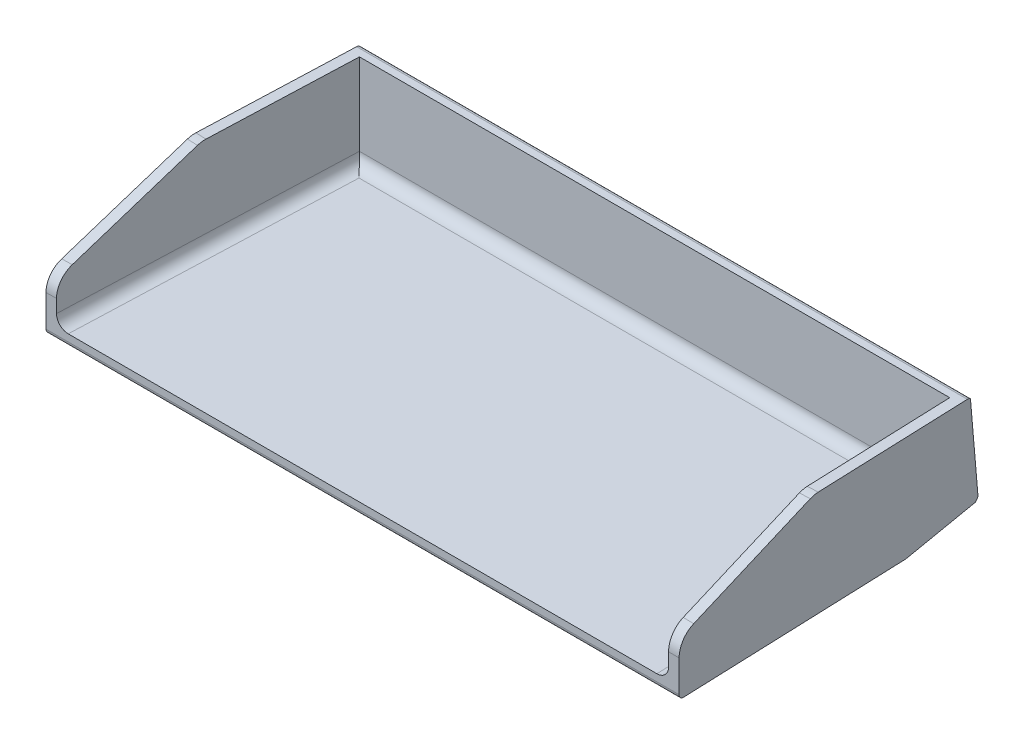
SolidWorks part; units mm, degrees
ref_plane "Front Plane" through (0, 0, 0) normal (0, 0, 1) x (1, 0, 0)
ref_plane "Top Plane" through (0, 0, 0) normal (0, 1, 0) x (1, 0, 0)
ref_plane "Right Plane" through (0, 0, 0) normal (1, 0, 0) x (0, 0, -1)
sketch "Sketch1" plane through (0, 0, 0) normal (0, 1, 0) x (1, 0, 0)
  line L6 (0, 0) -> (272, 0)
  line L7 (0, 0) -> (0, 134)
  line L8 (0, 134) -> (272, 134)
  line L9 (272, 0) -> (272, 134)
  dimension "D1" = 272
  dimension "D2" = 134
extrude "Boss-Extrude2" add sketch "Sketch1" along normal blind 45
sketch "Sketch8" plane through (0, 0, 0) normal (-1, 0, 0) x (0, 0, 1)
  line L0 (-134, 45) -> (-130, 45)
  line L1 (-134, 45) -> (0, 45) construction
  line L2 (-130, 45) -> (-134, 0)
  line L3 (-134, 0) -> (-134, 45)
  dimension "D1" = 4
extrude "Cut-Extrude8" cut sketch "Sketch8" against normal blind 300
sketch "Sketch9" plane through (0, 0, 0) normal (0, -1, 0) x (1, 0, 0)
  line L0 (0, -134) -> (5, -134)
  line L1 (272, -134) -> (0, -134) construction
  line L2 (5, -134) -> (0, 0)
  line L3 (0, 0) -> (0, -134)
  line L4 (272, -134) -> (267, -134)
  line L5 (267, -134) -> (272, 0)
  line L6 (272, 0) -> (272, -134)
  dimension "D1" = 5
  dimension "D2" = 5
extrude "Cut-Extrude10" cut sketch "Sketch9" against normal blind 300
sketch "Sketch11" plane through (0, 45, 0) normal (0, 1, 0) x (1, 0, 0)
  line L0 (9.6642, 125) -> (262.3358, 125)
  line L1 (4.8507, 130) -> (0, 0) construction
  line L3 (267.1493, 130) -> (4.8507, 130) construction
  line L4 (5, 0) -> (267, 0)
  line L5 (0, 0) -> (272, 0) construction
  line L6 (5, 0) -> (9.6642, 125)
  line L9 (262.3358, 125) -> (267, 0)
  point P8 (2.2406, 60.0487)
  dimension "D1" = 5
  dimension "D2" = 70
extrude "Cut-Extrude11" cut sketch "Sketch11" against normal blind 40
sketch "Sketch12" plane through (0, 0, 0) normal (-0.9993, 0, -0.0373) x (-0.0373, 0, 0.9993)
  line L0 (0, 45) -> (0, 0) construction
  line L1 (-130.0905, 45) -> (0, 45) construction
  line L2 (0, 22.5) -> (-60.0905, 45)
  line L3 (-60.0905, 45) -> (0, 45)
  line L4 (0, 45) -> (0, 22.5)
  point P0 (0, 22.5)
  point P1 (-60.0905, 45)
  dimension "D1" = 70
extrude "Cut-Extrude12" cut sketch "Sketch12" against normal blind 5
sketch "Sketch13" plane through (271.6218, 0, -10.1351) normal (0.9993, 0, -0.0373) x (-0.0373, 0, -0.9993)
  line L0 (-10.1422, 45) -> (-10.1422, 0) construction
  line L1 (-10.1422, 45) -> (119.9483, 45) construction
  line L2 (-10.1422, 22.5) -> (49.9483, 45)
  line L3 (49.9483, 45) -> (-10.1422, 45)
  line L4 (-10.1422, 45) -> (-10.1422, 22.5)
  point P0 (-10.1422, 22.5)
  point P1 (49.9483, 45)
  dimension "D1" = 70
extrude "Cut-Extrude13" cut sketch "Sketch13" against normal blind 5
fillet "Fillet1" radius 10 2 edges at (269.5, 22.5349, 0) (2.5, 22.5349, 0)
fillet "Fillet2" radius 5 3 edges at (264.6679, 5, -62.5) (136, 5, -125) (7.3321, 5, -62.5)
fillet "Fillet3" radius 10 2 edges at (267.2629, 45, -59.9555) (4.7371, 45, -59.9555)
fillet "Fillet5" radius 2 1 edges at (136, 0, 0)
fillet "Fillet6" radius 2 1 edges at (136, 0, -134)
fillet "Fillet7" radius 2 1 edges at (136, 45, -130)
sketch "Sketch17" plane through (0, 0, 0) normal (0, -1, 0) x (1, 0, 0)
  line L0 (4.9184, -131.8143) -> (267.0816, -131.8143) construction
  line L1 (0, 0) -> (242.4095, 0)
  line L2 (0, 0) -> (0, -131.8143)
  line L3 (0, -131.8143) -> (242.4095, -131.8143)
  line L6 (242.4095, -131.8143) -> (294.2291, -131.8143)
  line L8 (242.4095, 0) -> (294.2291, 0)
  line L9 (294.2291, -131.8143) -> (294.2291, 0)
extrude "Boss-Extrude3" add sketch "Sketch17" along normal blind 5
sketch "Sketch18" plane through (0, 0, 0) normal (0, 1, 0) x (1, 0, 0)
  line L9 (294.2291, 131.8143) -> (272.2234, 131.8143)
  line L10 (294.2291, 131.8143) -> (294.2291, 69.8677)
  line L11 (294.2291, 69.8677) -> (272.2234, 69.8677)
  line L12 (272.2234, 131.8143) -> (272.2234, 69.8677)
extrude "Boss-Extrude4" add sketch "Sketch18" along normal blind 5
sketch "Sketch19" plane through (0, 0, -131.8143) normal (0, 0, -1) x (-1, 0, 0)
  line L0 (0, -5) -> (-294.2291, -5) construction
  line L1 (-294.2291, 5) -> (-268.0644, 5)
  line L2 (-294.2291, 5) -> (-294.2291, -5)
  line L3 (-294.2291, -5) -> (-268.0644, -5)
  line L4 (-268.0644, 5) -> (-268.0644, -5)
extrude "Boss-Extrude5" add sketch "Sketch19" along normal blind 15
sketch "Sketch20" plane through (0, 5, 0) normal (0, 1, 0) x (1, 0, 0)
  line L0 (272.2234, 131.8143) -> (294.2291, 131.8143)
  line L1 (294.2291, 69.8677) -> (294.2291, 146.8143) construction
sketch "Sketch21" plane through (294.2291, 0, 0) normal (1, 0, 0) x (0, 0, -1)
  line L1 (146.8143, -5) -> (0, -5) construction
  line L2 (69.8677, -5) -> (131.8143, 5)
  line L3 (131.8143, 5) -> (146.8143, 5)
  line L4 (146.8143, 5) -> (146.8143, -5)
  line L5 (146.8143, -5) -> (69.8677, -5)
extrude "Cut-Extrude15" cut sketch "Sketch21" against normal blind 350
sketch "Sketch22" plane through (0, 5, 0) normal (0, 1, 0) x (1, 0, 0)
  line L1 (272.2234, 69.8677) -> (294.2291, 69.8677)
  line L2 (272.2234, 69.8677) -> (272.2234, 131.8143)
  line L3 (272.2234, 131.8143) -> (294.2291, 131.8143)
  line L4 (294.2291, 69.8677) -> (294.2291, 131.8143)
extrude "Cut-Extrude16" cut sketch "Sketch22" against normal blind 350
sketch "Sketch24" plane through (0, 0, 0) normal (0, 1, 0) x (1, 0, 0)
  line L0 (294.2291, 69.8677) -> (272.2234, 69.8677)
  line L1 (272.2234, 69.8677) -> (272.2234, 100.841)
  line L2 (272.2234, 100.841) -> (268.2373, 100.841)
  line L3 (268.2373, 100.841) -> (271.9254, 2)
  line L4 (271.9254, 2) -> (271.9254, 0)
  line L5 (294.2291, 0) -> (0, 0) construction
  line L6 (271.9254, 0) -> (294.2291, 0)
  line L7 (294.2291, 0) -> (294.2291, 69.8677)
extrude "Cut-Extrude17" cut sketch "Sketch24" against normal blind 350
sketch "Sketch26" plane through (0, -5, 0) normal (0, -1, 0) x (1, 0, 0)
  line L1 (271.9254, 0) -> (-95.0742, 0)
  line L2 (271.9254, 0) -> (271.9254, -253.0649)
  line L3 (271.9254, -253.0649) -> (-95.0742, -253.0649)
  line L4 (-95.0742, 0) -> (-95.0742, -253.0649)
extrude "Cut-Extrude18" cut sketch "Sketch26" against normal blind 5
fillet "Fillet8" radius 5 1 edges at (136, 5, -133.5556)
sketch "Sketch27" plane through (271.6218, 0, -10.1351) normal (0.9993, 0, -0.0373) x (-0.0373, 0, -0.9993)
  line L1 (-27.7463, -8.0877) -> (139.4987, -8.0877)
  line L2 (-27.7463, -8.0877) -> (-27.7463, 53.3809)
  line L3 (-27.7463, 53.3809) -> (139.4987, 53.3809)
  line L4 (139.4987, -8.0877) -> (139.4987, 53.3809)
  line L5 (-27.7463, -8.0877) -> (139.4987, 53.3809) construction
  line L6 (-27.7463, 53.3809) -> (139.4987, -8.0877) construction
  point P0 (55.8762, 22.6466)
extrude "Cut-Extrude19" cut sketch "Sketch27" against normal blind 0.5
sketch "Sketch28" plane through (0, 0, 0) normal (-0.9993, 0, -0.0373) x (-0.0373, 0, 0.9993)
  line L1 (-207.8458, -25.1656) -> (37.9381, -25.1656)
  line L2 (-207.8458, -25.1656) -> (-207.8458, 65.4325)
  line L3 (-207.8458, 65.4325) -> (37.9381, 65.4325)
  line L4 (37.9381, -25.1656) -> (37.9381, 65.4325)
  line L5 (-207.8458, -25.1656) -> (37.9381, 65.4325) construction
  line L6 (-207.8458, 65.4325) -> (37.9381, -25.1656) construction
  point P0 (-84.9539, 20.1334)
extrude "Cut-Extrude20" cut sketch "Sketch28" against normal blind 0.5
sketch "Sketch29" plane through (0, 11.8177, -132.9495) normal (0, 0.0885, -0.9961) x (-1, 0, 0)
  line L1 (-335.9704, 55.8131) -> (31.3149, 55.8131)
  line L2 (-335.9704, 55.8131) -> (-335.9704, -21.8749)
  line L3 (-335.9704, -21.8749) -> (31.3149, -21.8749)
  line L4 (31.3149, 55.8131) -> (31.3149, -21.8749)
  line L5 (-335.9704, 55.8131) -> (31.3149, -21.8749) construction
  line L6 (-335.9704, -21.8749) -> (31.3149, 55.8131) construction
  point P0 (-152.3277, 16.9691)
extrude "Cut-Extrude21" cut sketch "Sketch29" against normal blind 0.5
